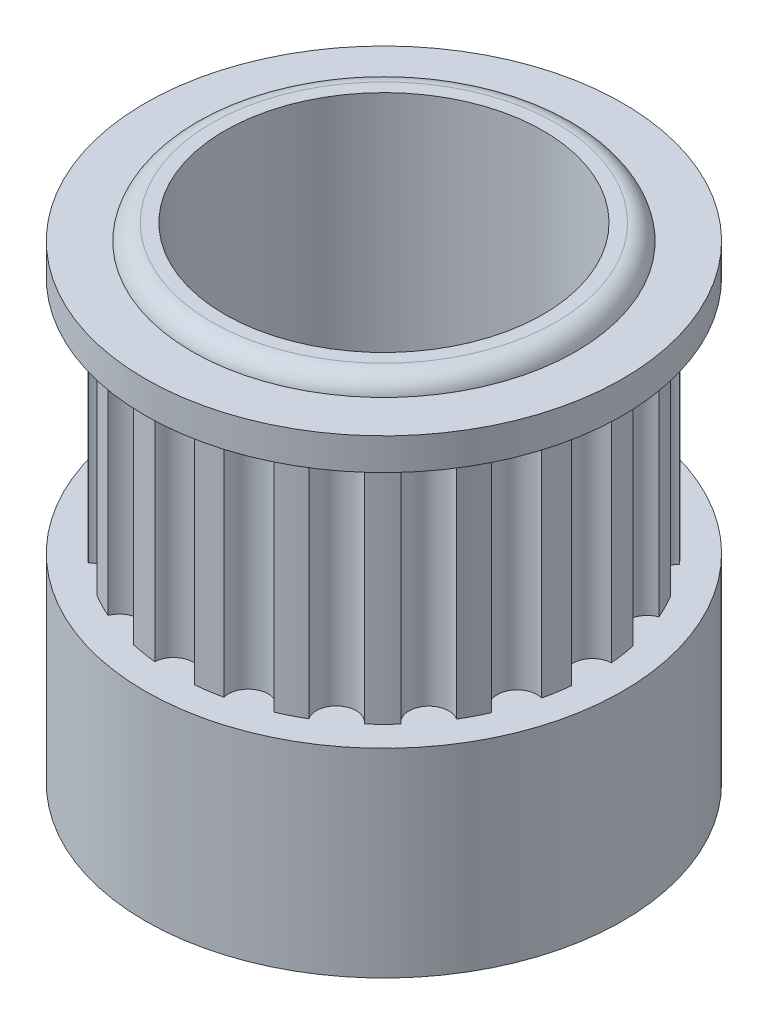
SolidWorks part; units mm, degrees
ref_plane "Front Plane" through (0, 0, 0) normal (0, 0, 1) x (1, 0, 0)
ref_plane "Top Plane" through (0, 0, 0) normal (0, 1, 0) x (1, 0, 0)
ref_plane "Right Plane" through (0, 0, 0) normal (1, 0, 0) x (0, 0, -1)
sketch "Sketch1" plane through (0, 0, 0) normal (0, 1, 0) x (1, 0, 0)
  circle A0 centre (0, 0) radius 6
  dimension "D1" = 12
extrude "Boss-Extrude1" add sketch "Sketch1" along normal blind 5
sketch "Sketch2" plane through (0, 5, 0) normal (0, 1, 0) x (1, 0, 0)
  circle A0 centre (0, 0) radius 5.2625
extrude "Boss-Extrude2" add sketch "Sketch2" along normal blind 6
sketch "Sketch3" plane through (0, 11, 0) normal (0, 1, 0) x (1, 0, 0)
  circle A0 centre (-1.6039, 5.0121) radius 0.5
  circle A1 centre (0, 0) radius 5.2625 construction
  circle A2 centre (0.0235, 5.2624) radius 0.5
  circle A3 centre (1.6485, 4.9976) radius 0.5
  circle A4 centre (3.1122, 4.2436) radius 0.5
  circle A5 centre (4.2712, 3.0742) radius 0.5
  circle A6 centre (5.0121, 1.6039) radius 0.5
  circle A7 centre (5.2624, -0.0235) radius 0.5
  circle A8 centre (4.9976, -1.6485) radius 0.5
  circle A9 centre (4.2436, -3.1122) radius 0.5
  circle A10 centre (3.0742, -4.2712) radius 0.5
  circle A11 centre (1.6039, -5.0121) radius 0.5
  circle A12 centre (-0.0235, -5.2624) radius 0.5
  circle A13 centre (-1.6485, -4.9976) radius 0.5
  circle A14 centre (-3.1122, -4.2436) radius 0.5
  circle A15 centre (-4.2712, -3.0742) radius 0.5
  circle A16 centre (-5.0121, -1.6039) radius 0.5
  circle A17 centre (-5.2624, 0.0235) radius 0.5
  circle A18 centre (-4.9976, 1.6485) radius 0.5
  circle A19 centre (-4.2436, 3.1122) radius 0.5
  circle A20 centre (-3.0742, 4.2712) radius 0.5
  dimension "D1" = 1
  dimension "D2" = 20
extrude "Cut-Extrude1" cut sketch "Sketch3" against normal blind 6
sketch "Sketch4" plane through (0, 11, 0) normal (0, 1, 0) x (1, 0, 0)
  circle A0 centre (0, 0) radius 6
extrude "Boss-Extrude3" add sketch "Sketch4" along normal blind 0.8
sketch "Sketch5" plane through (0, 11.8, 0) normal (0, 1, 0) x (1, 0, 0)
  circle A0 centre (0, 0) radius 4.8195
extrude "Boss-Extrude4" add sketch "Sketch5" along normal blind 0.4
fillet "Fillet3" radius 0.5 1 edges at (0, 12.2, 4.8195)
sketch "Sketch6" plane through (0, 12.2, 0) normal (0, 1, 0) x (1, 0, 0)
  circle A0 centre (0, 0) radius 4
  dimension "D1" = 8
extrude "Cut-Extrude2" cut sketch "Sketch6" against normal through all
